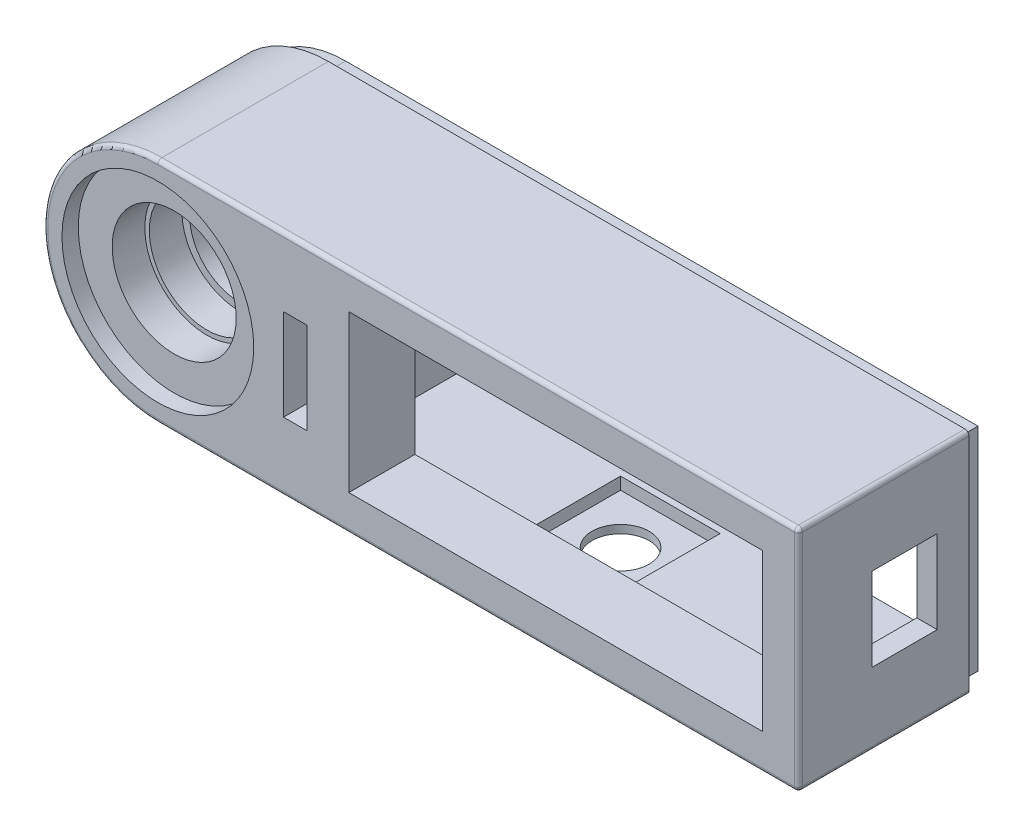
SolidWorks part; units mm, degrees
ref_plane "Спереди" through (0, 0, 0) normal (0, 0, 1) x (1, 0, 0)
ref_plane "Сверху" through (0, 0, 0) normal (0, 1, 0) x (1, 0, 0)
ref_plane "Справа" through (0, 0, 0) normal (1, 0, 0) x (0, 0, -1)
sketch "Эскиз1" plane through (0, 0, 0) normal (0, 0, 1) x (1, 0, 0)
  line L1 (39.25, -14) -> (-39.25, -14)
  line L2 (39.25, -14) -> (39.25, 14)
  line L3 (39.25, 14) -> (-39.25, 14)
  line L4 (-39.25, -14) -> (-39.25, 14) construction
  line L5 (39.25, -14) -> (-39.25, 14) construction
  line L6 (39.25, 14) -> (-39.25, -14) construction
  arc A0 (-39.25, 14) -> (-39.25, -14) centre (-39.25, 0) ccw
  point P1 (0, 0)
  dimension "D1" = 14
  dimension "D2" = 78.5
extrude "Бобышка-Вытянуть1" add sketch "Эскиз1" along normal blind 23
sketch "Эскиз2" plane through (0, 0, 23) normal (0, 0, 1) x (1, 0, 0)
  circle A0 centre (-39.25, 0) radius 11.75
  dimension "D1" = 23.5
extrude "Вырез-Вытянуть1" cut sketch "Эскиз2" against normal blind 2
sketch "Эскиз3" plane through (0, 0, 21) normal (0, 0, 1) x (1, 0, 0)
  circle A0 centre (-39.25, 0) radius 7.6
  dimension "D1" = 15.2
extrude "Вырез-Вытянуть2" cut sketch "Эскиз3" against normal blind 4
sketch "Эскиз4" plane through (0, 0, 17) normal (0, 0, 1) x (1, 0, 0)
  circle A0 centre (-39.25, 0) radius 7.05
  dimension "D1" = 14.1
extrude "Вырез-Вытянуть3" cut sketch "Эскиз4" against normal blind 4
sketch "Эскиз5" plane through (0, 0, 13) normal (0, 0, 1) x (1, 0, 0)
  circle A0 centre (-39.25, 0) radius 6.1
  dimension "D1" = 12.2
extrude "Вырез-Вытянуть4" cut sketch "Эскиз5" against normal blind 4
sketch "Эскиз6" plane through (0, 0, 9) normal (0, 0, 1) x (1, 0, 0)
  circle A0 centre (-39.25, 0) radius 2.6
  dimension "D1" = 5.2
extrude "Вырез-Вытянуть5" cut sketch "Эскиз6" against normal blind 9
sketch "Эскиз7" plane through (0, 0, 0) normal (0, 0, -1) x (-1, 0, 0)
  circle A0 centre (39.25, 0) radius 3
  dimension "D1" = 6
extrude "Вырез-Вытянуть6" cut sketch "Эскиз7" against normal blind 1.1
sketch "Эскиз8" plane through (0, 0, 23) normal (0, 0, 1) x (1, 0, 0)
  line L0 (-53.25, 0) -> (39.25, 0) construction
  line L1 (-15.85, 9.6) -> (34.85, 9.6)
  line L2 (-15.85, 9.6) -> (-15.85, -9.6)
  line L3 (-15.85, -9.6) -> (34.85, -9.6)
  line L4 (34.85, 9.6) -> (34.85, -9.6)
  line L5 (39.25, -14) -> (39.25, 14) construction
  line L6 (-39.25, -14) -> (39.25, -14) construction
  arc A0 (-39.25, 14) -> (-39.25, -14) centre (-39.25, 0) ccw construction
  point P12 (-15.85, 0)
  dimension "D1" = 19.2
  dimension "D2" = 50.7
  dimension "D3" = 4.4
  dimension "D4" = 4.4
extrude "Вырез-Вытянуть7" cut sketch "Эскиз8" against normal blind 8.1
sketch "Эскиз9" plane through (0, 0, 0) normal (0, 0, -1) x (-1, 0, 0)
  line L0 (-39.25, 0) -> (53.25, 0) construction
  line L1 (-39.25, -14) -> (-39.25, 14) construction
  line L2 (-36.75, -11.5) -> (-39.25, -11.5) construction
  line L3 (-36.75, 11.5) -> (23.75, 11.5)
  line L4 (-36.75, 11.5) -> (-36.75, -11.5)
  line L5 (-36.75, -11.5) -> (23.75, -11.5)
  line L6 (23.75, 11.5) -> (23.75, -11.5)
  line L7 (-36.75, -11.5) -> (-36.75, -14) construction
  line L8 (39.25, -14) -> (-39.25, -14) construction
  line L9 (-36.75, 11.5) -> (-36.75, 14) construction
  line L10 (-39.25, 14) -> (39.25, 14) construction
  circle A0 centre (39.25, 0) radius 14 construction
  point P11 (-36.75, 0)
  dimension "D1" = 2.5
  dimension "D2" = 15.5
extrude "Вырез-Вытянуть8" cut sketch "Эскиз9" against normal up to surface (14.9 mm away) up to face at (9.5, 0, 14.9)
sketch "Эскиз10" plane through (39.25, 0, 0) normal (1, 0, 0) x (0, 0, -1)
  line L0 (-23, -14) -> (-23, 14) construction
  line L1 (-14, -5.1) -> (-6, -5.1)
  line L2 (-14, -5.1) -> (-14, 5.1)
  line L3 (-14, 5.1) -> (-6, 5.1)
  line L4 (-6, -5.1) -> (-6, 5.1)
  line L5 (-14, -5.1) -> (-6, 5.1) construction
  line L6 (-14, 5.1) -> (-6, -5.1) construction
  point P0 (-10, 0)
  point P11 (-23, 0)
  dimension "D1" = 17
  dimension "D3" = 8
  dimension "D4" = 10.2
extrude "Вырез-Вытянуть9" cut sketch "Эскиз10" against normal up to next
sketch "Эскиз11" plane through (0, 0, 0) normal (0, 0, -1) x (-1, 0, 0)
  line L6 (39.25, 13) -> (-38.25, 13)
  line L7 (-38.25, 13) -> (-38.25, -13)
  line L8 (-38.25, -13) -> (39.25, -13)
  line L9 (39.25, 13) -> (-38.25, 13)
  line L10 (-38.25, 13) -> (-38.25, -13)
  line L11 (-38.25, -13) -> (39.25, -13)
  arc A2 (39.25, -13) -> (39.25, 13) centre (39.25, 0) ccw
  arc A3 (39.25, -13) -> (39.25, 13) centre (39.25, 0) ccw
  dimension "D1" = 1
extrude "Вырез-Вытянуть-Тонкостенный1" cut sketch "Эскиз11" against normal blind 2.1 thin thin type one direction wall 2
sketch "Эскиз13" plane through (0, -11.5, 0) normal (0, 1, 0) x (1, 0, 0)
  line L1 (-2.85, -14.9) -> (9.35, -14.9)
  line L2 (-2.85, -14.9) -> (-2.85, -2.7)
  line L3 (-2.85, -2.7) -> (9.35, -2.7)
  line L4 (9.35, -14.9) -> (9.35, -2.7)
  line L5 (-2.85, -14.9) -> (9.35, -2.7) construction
  line L6 (-2.85, -2.7) -> (9.35, -14.9) construction
  line L7 (36.75, -14.9) -> (-23.75, -14.9) construction
  point P8 (3.25, -8.8)
  dimension "D1" = 12.2
extrude "Вырез-Вытянуть11" cut sketch "Эскиз13" against normal offset from surface (1.5 mm away) 1 up to face at (0, -14, 12.55)
sketch "Эскиз16" plane through (0, -13, 0) normal (0, 1, 0) x (1, 0, 0)
  line L0 (9.35, -2.7) -> (-2.85, -14.9) construction
  line L1 (9.35, -14.9) -> (-2.85, -2.7) construction
  circle A0 centre (3.25, -8.8) radius 3.5
  point P8 (3.25, -8.8)
  dimension "D1" = 7
extrude "Вырез-Вытянуть14" cut sketch "Эскиз16" against normal up to next
sketch "Эскиз14" plane through (0, 0, 14.9) normal (0, 0, -1) x (-1, 0, 0)
  line L0 (15.85, 9.6) -> (15.85, -9.6) construction
  line L1 (23.75, -5.5) -> (21.05, -5.5)
  line L2 (23.75, -5.5) -> (23.75, 5.5)
  line L3 (23.75, 5.5) -> (21.05, 5.5)
  line L4 (21.05, -5.5) -> (21.05, 5.5)
  line L5 (23.75, -5.5) -> (21.05, 5.5) construction
  line L6 (23.75, 5.5) -> (21.05, -5.5) construction
  line L7 (23.75, -11.5) -> (23.75, 11.5) construction
  point P0 (22.4, 0)
  point P9 (15.85, 0)
  dimension "D1" = 11
  dimension "D2" = 2.7
extrude "Вырез-Вытянуть12" cut sketch "Эскиз14" against normal blind 12
sketch "Эскиз15" plane through (0, 0, 23) normal (0, 0, 1) x (1, 0, 0)
  line L8 (-23.85, -5.6) -> (-20.95, -5.6)
  line L9 (-23.85, 5.6) -> (-23.85, -5.6)
  line L10 (-20.95, 5.6) -> (-23.85, 5.6)
  line L11 (-20.95, -5.6) -> (-20.95, 5.6)
  line L12 (-23.85, -5.6) -> (-20.95, -5.6)
  line L13 (-23.85, 5.6) -> (-23.85, -5.6)
  line L14 (-20.95, 5.6) -> (-23.85, 5.6)
  line L15 (-20.95, -5.6) -> (-20.95, 5.6)
  dimension "D1" = 0.1
extrude "Вырез-Вытянуть13" cut sketch "Эскиз15" against normal offset from surface (5.6 mm away) 2.5 up to face at (9.5, 0, 14.9)
sketch "Эскиз17" plane through (0, 0, 9) normal (0, 0, 1) x (1, 0, 0)
  circle A0 centre (-39.25, 0) radius 5
  dimension "D1" = 10
ref_plane "Плоскость1" through (0, 0, 3.1) normal (0, 0, -1) x (-1, 0, 0)
sketch "Эскиз18" plane through (0, 0, 3.1) normal (0, 0, -1) x (-1, 0, 0)
  circle A0 centre (39.25, 0) radius 2.6 construction
  circle A1 centre (39.25, 0) radius 2.6
loft "Вырез-По сечениям2" cut profiles "Эскиз17", "Эскиз18" connector at (-34.25, 0, 9) connector at (-36.655, 0.1615, 3.1)
fillet "Скругление1" radius 0.5 6 edges at (0, -14, 23) (-53.25, 0, 23) (0, 14, 23) (39.25, 0, 23) (39.25, -14, 12.55) (39.25, 14, 12.55)
